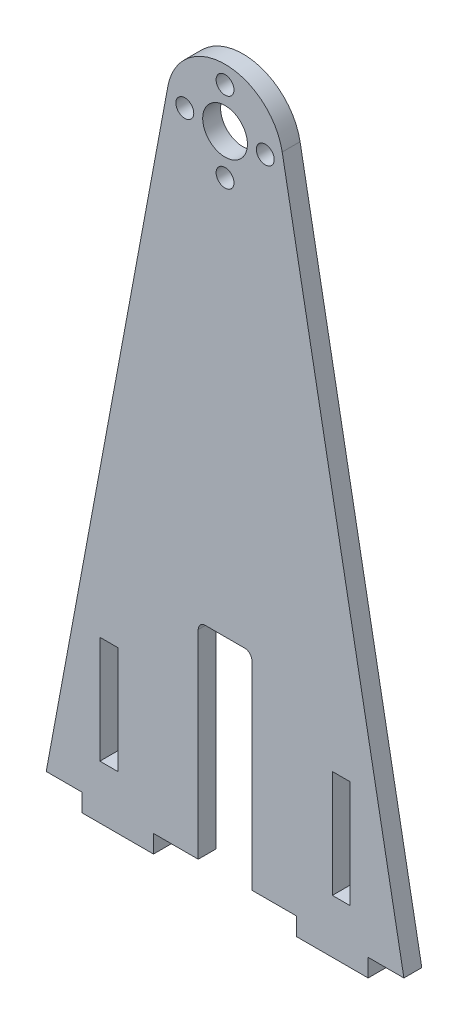
SolidWorks part; units mm, degrees
material "Pine"
ref_plane "Front Plane" through (0, 0, 0) normal (0, 0, 1) x (1, 0, 0)
ref_plane "Top Plane" through (0, 0, 0) normal (0, 1, 0) x (1, 0, 0)
ref_plane "Right Plane" through (0, 0, 0) normal (1, 0, 0) x (0, 0, -1)
sketch "Sketch1" plane through (0, 0, 0) normal (0, 0, 1) x (1, 0, 0)
  line L0 (0, 0) -> (0, 228.6) construction
  line L1 (25.4, 0) -> (9.525, 0)
  line L2 (-25.4, 0) -> (-25.4, -6.35)
  line L3 (-25.4, -6.35) -> (-50.8, -6.35)
  line L4 (-50.8, -6.35) -> (-50.8, 0)
  line L5 (-50.8, 0) -> (-63.5, 0)
  line L6 (-63.5, 0) -> (-20.2897, 232.3729)
  line L7 (0, 228.6) -> (0, 159.1888) construction
  line L8 (50.8, 0) -> (63.5, 0)
  line L9 (50.8, -6.35) -> (50.8, 0)
  line L10 (25.4, 0) -> (25.4, -6.35)
  line L11 (25.4, -6.35) -> (50.8, -6.35)
  line L12 (63.5, 0) -> (20.2897, 232.3729)
  line L13 (44.45, 12.7) -> (38.1, 12.7)
  line L14 (-44.45, 12.7) -> (-38.1, 12.7)
  line L15 (-44.45, 12.7) -> (-44.45, 50.8)
  line L16 (-44.45, 50.8) -> (-38.1, 50.8)
  line L17 (-38.1, 12.7) -> (-38.1, 50.8)
  line L22 (44.45, 12.7) -> (44.45, 50.8)
  line L23 (44.45, 50.8) -> (38.1, 50.8)
  line L24 (38.1, 12.7) -> (38.1, 50.8)
  line L25 (-9.525, 73.1663) -> (9.525, 73.1663)
  line L26 (9.525, 73.1663) -> (9.525, 0)
  line L27 (-38.1, 0) -> (-38.1, 12.7) construction
  line L28 (-44.45, 12.7) -> (-44.45, 0) construction
  line L30 (-9.525, 73.1663) -> (-9.525, 0)
  line L31 (-9.525, 0) -> (-25.4, 0)
  arc A0 (20.2897, 232.3729) -> (-20.2897, 232.3729) centre (0, 228.6) ccw
  circle A1 centre (0, 228.6) radius 7.9375
  circle A3 centre (0, 242.8875) radius 3.175
  circle A4 centre (14.2875, 228.6) radius 3.175
  circle A5 centre (0, 214.3125) radius 3.175
  circle A6 centre (-14.2875, 228.6) radius 3.175
  point P42 (0, 228.6)
  point P43 (0, 73.1663)
  dimension "D5" = 12.7
  dimension "D7" = 15.875
  dimension "D8" = 19.05
  dimension "D13" = 6.35
  dimension "D1" = 63.5
  dimension "D2" = 6.35
  dimension "D3" = 25.4
  dimension "D4" = 25.4
  dimension "D6" = 228.6
  dimension "D10" = 38.1
  dimension "D11" = 12.7
  dimension "D12" = 14.2875
  dimension "D14" = 4
extrude "Boss-Extrude1" add sketch "Sketch1" along normal blind 6.35
fillet "Fillet1" radius 2.54 1 edges at (-9.525, 73.1663, 3.175)
fillet "Fillet2" radius 2.54 1 edges at (9.525, 73.1663, 3.175)
